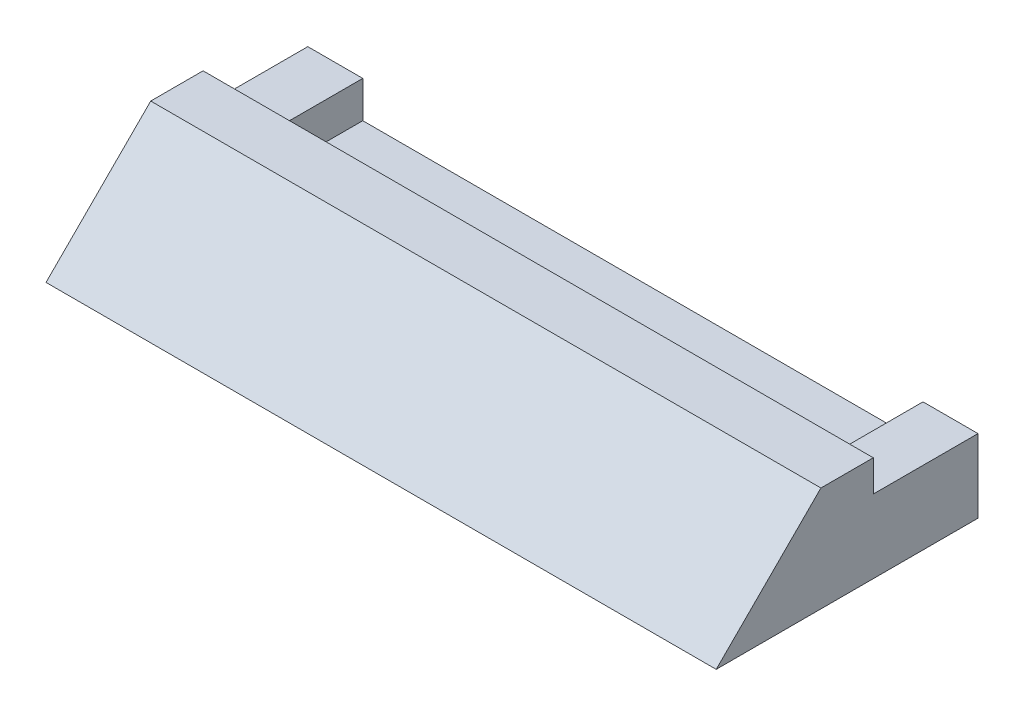
SolidWorks part; units mm, degrees
material "1060 Alloy"
ref_plane "Front Plane" through (0, 0, 0) normal (0, 0, 1) x (1, 0, 0)
ref_plane "Top Plane" through (0, 0, 0) normal (0, 1, 0) x (1, 0, 0)
ref_plane "Right Plane" through (0, 0, 0) normal (1, 0, 0) x (0, 0, -1)
sketch "Sketch1" plane through (0, 0, 0) normal (1, 0, 0) x (0, 0, -1)
  line L0 (0, 0) -> (10, 10)
  line L1 (10, 10) -> (25, 10)
  line L2 (25, 10) -> (25, 0)
  line L3 (25, 0) -> (0, 0)
  dimension "D1" = 45
  dimension "D2" = 10
  dimension "D3" = 15
extrude "Boss-Extrude1" add sketch "Sketch1" along normal blind 64
sketch "Sketch3" plane through (0, 10, 0) normal (0, 1, 0) x (1, 0, 0)
  line L0 (64, 25) -> (0, 25) construction
  line L1 (5.25, 25) -> (58.75, 25)
  line L2 (5.25, 25) -> (5.25, 15)
  line L3 (5.25, 15) -> (58.75, 15)
  line L4 (58.75, 25) -> (58.75, 15)
  line L5 (0, 25) -> (0, 10) construction
  dimension "D1" = 53.5
  dimension "D2" = 5.25
  dimension "D3" = 10
extrude "Cut-Extrude2" cut sketch "Sketch3" against normal blind 6.5
sketch "Sketch4" plane through (0, 3.5, 0) normal (0, 1, 0) x (1, 0, 0)
  line L0 (5.25, 15) -> (58.75, 15) construction
  line L1 (5.25, 25) -> (5.25, 15) construction
  line L2 (5.25, 25) -> (5.25, 15) construction
  line L3 (58.75, 15) -> (58.75, 25) construction
  circle A0 centre (10.25, 20) radius 1.5
  circle A1 centre (32, 20) radius 1.5
  circle A2 centre (53.75, 20) radius 1.5
  dimension "D1" = 3
  dimension "D2" = 5
  dimension "D3" = 5
  dimension "D4" = 26.75
  dimension "D5" = 5
extrude "Cut-Extrude3" cut sketch "Sketch4" against normal up to next
sketch "Sketch5" plane through (0, 10, 0) normal (0, 1, 0) x (1, 0, 0)
  line L0 (64, 25) -> (64, 10) construction
  line L1 (0, 25) -> (64, 25)
  line L2 (0, 25) -> (0, 15)
  line L3 (0, 15) -> (64, 15)
  line L4 (64, 25) -> (64, 15)
  line L5 (5.25, 15) -> (58.75, 15) construction
extrude "Cut-Extrude4" cut sketch "Sketch5" against normal offset from surface (3 mm away) 3.5 up to face at (53.75, 3.5, -18.5)
